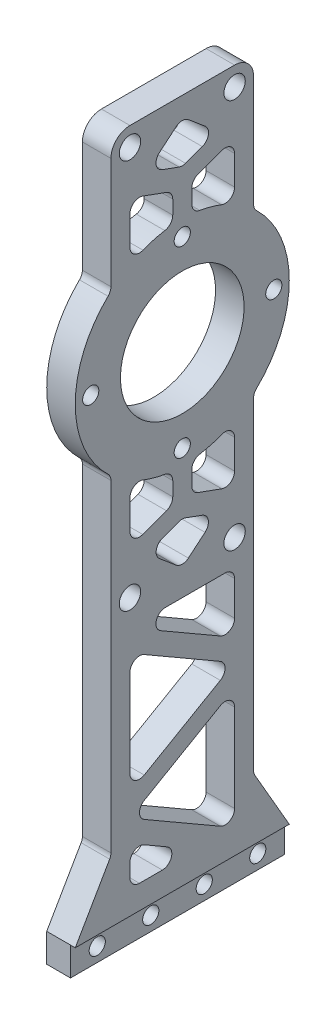
SolidWorks part; units mm, degrees
material "Сплав 2024"
ref_plane "Спереди" through (0, 0, 0) normal (0, 0, 1) x (1, 0, 0)
ref_plane "Сверху" through (0, 0, 0) normal (0, 1, 0) x (1, 0, 0)
ref_plane "Справа" through (0, 0, 0) normal (1, 0, 0) x (0, 0, -1)
sketch "Эскиз1" plane through (0, 0, 0) normal (0, 1, 0) x (1, 0, 0)
  line L1 (0, 0) -> (6, 0)
  line L2 (0, 0) -> (0, -30)
  line L3 (0, -30) -> (6, -30)
  line L4 (6, 0) -> (6, -30)
  dimension "D1" = 6
  dimension "D2" = 30
extrude "Бобышка-Вытянуть1" add sketch "Эскиз1" along normal blind 177
sketch "Эскиз2" plane through (0, 0, 0) normal (-1, 0, 0) x (0, 0, 1)
  line L0 (30, 105) -> (0, 105) construction
  line L3 (15, 177) -> (15, 0) construction
  line L4 (0, 177) -> (30, 177) construction
  line L5 (0, 0) -> (30, 0) construction
  line L6 (30, 0) -> (0, 0) construction
  circle A0 centre (15, 105) radius 22.5
  dimension "D1" = 45
  dimension "D2" = 105
extrude "Бобышка-Вытянуть2" add sketch "Эскиз2" against normal up to surface (6 mm away) up to face at (6, 88.5, 15)
sketch "Эскиз3" plane through (0, 0, 0) normal (-1, 0, 0) x (0, 0, 1)
  circle A0 centre (15, 105) radius 13
  dimension "D1" = 26
extrude "Вырез-Вытянуть1" cut sketch "Эскиз3" against normal through all
sketch "Эскиз4" plane through (6, 0, 0) normal (-1, 0, 0) x (0, 0, 1)
  line L0 (-7.5, 105) -> (37.5, 105) construction
  line L2 (15, 127.5) -> (15, 82.5) construction
  line L3 (30, 105) -> (0, 105) construction
  circle A0 centre (15, 105) radius 19.25 construction
  circle A1 centre (15, 105) radius 22.5 construction
  dimension "D1" = 38.5
  dimension "D2" = 90
hole_wizard "Отверстие с зазором M32" positions "Эскиз6" profile "Эскиз5" hole size "M3" standard "Ansi Metric" end condition up to next
sketch "Эскиз6" plane through (6, -25.0247, 7.2629) normal (-1, 0, 0) x (0, 0, 1)
  line L0 (-14.7629, 130.0247) -> (30.2371, 130.0247) construction
  line L1 (7.7371, 152.5247) -> (7.7371, 107.5247) construction
  circle A0 centre (7.7371, 130.0247) radius 19.25 construction
  point P0 (-11.5129, 130.0247)
  point P6 (7.7371, 110.7747)
  point P10 (26.9871, 130.0247)
  point P12 (7.7371, 149.2747)
sketch "Эскиз5" plane through (6, 105, -4.25) normal (0, 1, 0) x (0, 0, -1)
  line L0 (0, 0) -> (0, 6)
  line L1 (0, 6) -> (1.7, 6)
  line L2 (1.7, 6) -> (1.7, 0)
  line L5 (1.7, 0) -> (0, 0)
  line L11 (0, -6.35) -> (0, 107.95) construction
  dimension "Диаметр сквозного отверстия" = 3.4
  dimension "Глубина сквозного отверстия" = 6
sketch "Эскиз8" plane through (6, 0, 0) normal (1, 0, 0) x (0, 0, -1)
  line L0 (-15, 177) -> (-15, 0) construction
  line L1 (-30, 177) -> (0, 177) construction
  line L2 (-30, 0) -> (0, 0) construction
  line L3 (19.447, 105) -> (-49.447, 105) construction
  line L4 (0, 177) -> (0, 121.7705) construction
  line L5 (-26, 146) -> (-4, 146) construction
  line L6 (-26, 146) -> (-26, 64) construction
  line L7 (-26, 64) -> (-4, 64) construction
  line L8 (-4, 146) -> (-4, 64) construction
  line L9 (-26, 146) -> (-4, 64) construction
  line L11 (-30, 105) -> (0, 105) construction
  point P8 (-15, 105)
  point P9 (-15, 105)
  dimension "D1" = 4
  dimension "D2" = 82
  dimension "D4" = 22
hole_wizard "Отверстие с зазором M41" positions "Эскиз10" profile "Эскиз9" hole size "M4" standard "Ansi Metric" end condition through all
sketch "Эскиз10" plane through (6, 0, 0) normal (1, 0, 0) x (0, 0, -1)
  point P0 (-26, 146)
  point P3 (-4, 146)
  point P6 (-4, 64)
  point P9 (-26, 64)
sketch "Эскиз9" plane through (6, 146, 26) normal (0, 1, 0) x (0, 0, -1)
  line L0 (0, 0) -> (0, 6)
  line L1 (0, 6) -> (2.25, 6)
  line L2 (2.25, 6) -> (2.25, 0)
  line L5 (2.25, 0) -> (0, 0)
  line L11 (0, -6.35) -> (0, 107.95) construction
  dimension "Диаметр сквозного отверстия" = 4.5
  dimension "Глубина сквозного отверстия" = 6
sketch "Эскиз11" plane through (6, 0, 0) normal (1, 0, 0) x (0, 0, -1)
  line L0 (-30, 0) -> (0, 0) construction
  line L1 (-15, 177) -> (-15, 0) construction
  line L2 (-30, 177) -> (0, 177) construction
  line L3 (0, 88.2295) -> (0, 0) construction
  line L4 (-30, 88.2295) -> (-30, 0) construction
  line L5 (-37.5, 3) -> (7.5, 3) construction
  line L6 (-9.375, 6) -> (-9.375, 0) construction
  line L7 (-3.75, 6) -> (-3.75, 0) construction
  line L8 (1.875, 6) -> (1.875, 0) construction
  line L20 (-15, 0) -> (-15, 6) construction
  line L21 (-20.625, 0) -> (-20.625, 6) construction
  line L22 (-26.25, 0) -> (-26.25, 6) construction
  line L23 (-31.875, 0) -> (-31.875, 6) construction
  line L25 (-37.5, 0) -> (7.5, 6) construction
  line L26 (-37.5, 6) -> (7.5, 0) construction
  line L27 (-37.5, 6) -> (7.5, 6) construction
  line L28 (0, 18.9904) -> (7.5, 6)
  line L29 (-30, 18.9904) -> (0, 18.9904)
  line L30 (7.5, 6) -> (7.5, 0)
  line L31 (-37.5, 0) -> (7.5, 0)
  line L32 (-37.5, 6) -> (-37.5, 0)
  line L33 (-37.5, 6) -> (-30, 18.9904)
  point P2 (-15, 3)
  dimension "D1" = 45
  dimension "D2" = 6
  dimension "D3" = 5.625
  dimension "D4" = 5.625
  dimension "D5" = 5.625
  dimension "D6" = 5.625
  dimension "D7" = 120
  dimension "D8" = 5.625
  dimension "D9" = 5.625
  dimension "D10" = 5.625
extrude "Бобышка-Вытянуть3" add sketch "Эскиз11" against normal up to surface (6 mm away) up to face at (0, 146, 23.75)
hole_wizard "Отверстие с зазором M31" positions "Эскиз13" profile "Эскиз12" hole size "M3" standard "Ansi Metric" end condition through all
sketch "Эскиз13" plane through (6, 0, 0) normal (1, 0, 0) x (0, 0, -1)
  line L4 (-31.875, 0) -> (-31.875, 6) construction
  line L8 (1.875, 6) -> (1.875, 0) construction
  line L9 (-9.375, 6) -> (-9.375, 0) construction
  line L10 (-20.625, 0) -> (-20.625, 6) construction
  point P16 (-31.875, 3)
  point P20 (-20.625, 3)
  point P24 (-9.375, 3)
  point P28 (1.875, 3)
sketch "Эскиз12" plane through (6, 3, 31.875) normal (0, 1, 0) x (0, 0, -1)
  line L0 (0, 0) -> (0, 6)
  line L1 (0, 6) -> (1.7, 6)
  line L2 (1.7, 6) -> (1.7, 0)
  line L5 (1.7, 0) -> (0, 0)
  line L11 (0, -6.35) -> (0, 107.95) construction
  dimension "Диаметр сквозного отверстия" = 3.4
  dimension "Глубина сквозного отверстия" = 6
sketch "Эскиз14" plane through (6, 0, 0) normal (1, 0, 0) x (0, 0, -1)
  line L5 (-37.5, 0) -> (7.5, 0)
  line L6 (-37.5, 0) -> (-37.5, 6)
  line L7 (-37.5, 6) -> (7.5, 6)
  line L8 (7.5, 0) -> (7.5, 6)
extrude "Вырез-Вытянуть2" cut sketch "Эскиз14" against normal blind 1
sketch "Эскиз15" plane through (6, 0, 0) normal (1, 0, 0) x (0, 0, -1)
  line L0 (0, 177) -> (0, 121.7705) construction
  line L1 (-30, 177) -> (0, 177)
  line L2 (-30, 177) -> (-30, 150)
  line L3 (-30, 150) -> (0, 150)
  line L4 (0, 177) -> (0, 150)
  circle A0 centre (-26, 146) radius 2.25 construction
  dimension "D1" = 4
extrude "Вырез-Вытянуть3" cut sketch "Эскиз15" against normal up to surface (6 mm away) up to face at (0, 3, 30.175)
fillet "Скругление1" radius 4 2 edges at (3, 150, 30) (3, 150, 0)
sketch "Эскиз16" plane through (0, 0, 0) normal (-1, 0, 0) x (0, 0, 1)
  line L0 (4, 0) -> (4, 150) construction
  line L1 (-7.5, 0) -> (37.5, 0) construction
  line L2 (4, 150) -> (26, 150) construction
  line L3 (26, 0) -> (26, 150) construction
  line L4 (0, 88.2295) -> (0, 18.9904) construction
  line L5 (30, 88.2295) -> (30, 18.9904) construction
  line L6 (15, 177) -> (15, 0) construction
  line L7 (0, 146) -> (30, 146) construction
  line L8 (0, 146) -> (0, 121.7705) construction
  line L9 (30, 146) -> (30, 121.7705) construction
  line L10 (15, 146) -> (4, 136.7699) construction
  line L11 (15, 146) -> (26, 136.7699) construction
  line L12 (0, 136.7699) -> (30, 136.7699) construction
  line L13 (4, 136.7699) -> (4, 124.6278)
  line L14 (26, 136.7699) -> (26, 124.6278)
  line L15 (13, 133.4942) -> (13, 127.4109)
  line L16 (17, 133.4942) -> (17, 127.4109)
  line L17 (4, 136.7699) -> (13, 133.4942)
  line L18 (0, 133.4942) -> (30, 133.4942) construction
  line L19 (26, 136.7699) -> (17, 133.4942)
  line L20 (7.5382, 139.7388) -> (15, 137.0229)
  line L21 (22.4618, 139.7388) -> (15, 137.0229)
  line L22 (7.5382, 139.7388) -> (15, 146)
  line L23 (15, 146) -> (22.4618, 139.7388)
  line L24 (15, 105) -> (22.4618, 105) construction
  line L25 (13, 76.4791) -> (13, 82.5891)
  line L26 (17, 76.4791) -> (17, 82.5891)
  line L27 (26, 73.2033) -> (17, 76.4791)
  line L28 (26, 73.2033) -> (26, 85.3722)
  line L29 (4, 73.2033) -> (4, 85.3722)
  line L30 (4, 73.2033) -> (13, 76.4791)
  line L31 (7.5605, 70.2425) -> (15, 72.9503)
  line L32 (22.4395, 70.2425) -> (15, 72.9503)
  line L33 (15, 64) -> (22.4395, 70.2425)
  line L34 (7.5605, 70.2425) -> (15, 64)
  line L35 (26, 53.8812) -> (26, 28.4778)
  line L36 (26, 28.4778) -> (4, 41.1795)
  line L37 (4, 41.1795) -> (26, 53.8812)
  line L38 (4, 58.5) -> (26, 58.5)
  line L39 (26, 58.5) -> (4, 45.7983)
  line L40 (4, 45.7983) -> (4, 58.5)
  line L41 (4, 36.5607) -> (26, 23.859)
  line L42 (26, 23.859) -> (4, 11.1573)
  line L43 (4, 11.1573) -> (4, 36.5607)
  line L44 (11.7276, 11) -> (26, 19.2402)
  line L45 (26, 19.2402) -> (26, 11)
  line L46 (26, 11) -> (11.7276, 11)
  line L47 (34.6132, 11) -> (-4.6132, 11) construction
  line L48 (30, 18.9904) -> (37.5, 6) construction
  line L49 (-7.5, 6) -> (0, 18.9904) construction
  line L50 (-7.5, 6) -> (37.5, 6) construction
  line L51 (0, 76.4791) -> (30, 76.4791) construction
  line L52 (0, 73.2033) -> (30, 73.2033) construction
  line L53 (0, 70.2425) -> (30, 70.2425) construction
  line L54 (26, 64) -> (4, 64) construction
  circle A0 centre (15, 105) radius 22.5 construction
  arc A1 (4, 124.6278) -> (13, 127.4109) centre (15, 105) cw
  arc A2 (17, 127.4109) -> (26, 124.6278) centre (15, 105) cw
  arc A3 (17, 82.5891) -> (26, 85.3722) centre (15, 105) ccw
  arc A4 (4, 85.3722) -> (13, 82.5891) centre (15, 105) ccw
  circle A5 centre (4, 64) radius 2.25 construction
  point P12 (4, 124.6278)
  point P13 (26, 124.6278)
  point P20 (15, 146)
  dimension "D3" = 4
  dimension "D16" = 5.5
  dimension "D1" = 4
  dimension "D2" = 4
  dimension "D4" = 100
  dimension "D5" = 4
  dimension "D6" = 2
  dimension "D7" = 4
  dimension "D8" = 110
  dimension "D9" = 30
  dimension "D10" = 4
  dimension "D11" = 4
  dimension "D12" = 4
  dimension "D13" = 60
  dimension "D14" = 60
  dimension "D15" = 5
  dimension "D17" = 6.11
  dimension "D18" = 4
  dimension "D19" = 2
  dimension "D20" = 110
  dimension "D21" = 4
  dimension "D22" = 100
extrude "Вырез-Вытянуть4" cut sketch "Эскиз16" against normal through all
fillet "Скругление3" radius 2 42 edges at (3, 127.4109, 13) (3, 124.6278, 26) (3, 124.6278, 4) (3, 127.4109, 17) (3, 133.4942, 17) (3, 136.7699, 4) (3, 133.4942, 13) (3, 136.7699, 26) (3, 137.0229, 15) (3, 139.7388, 22.4618) (3, 139.7388, 7.5382) (3, 146, 15) (3, 70.2425, 7.5605) (3, 70.2425, 22.4395) (3, 85.3722, 4) (3, 76.4791, 17) (3, 82.5891, 17) (3, 73.2033, 4) (3, 64, 15) (3, 72.9503, 15) (3, 82.5891, 13) (3, 85.3722, 26) (3, 76.4791, 13) (3, 73.2033, 26) (3, 11, 11.7276) (3, 11, 26) (3, 11.1573, 4) (3, 19.2402, 26) (3, 23.859, 26) (3, 28.4778, 26) (3, 36.5607, 4) (3, 53.8812, 26) (3, 41.1795, 4) (3, 45.7983, 4) (3, 58.5, 4) (3, 58.5, 26) (3, 18.9904, 30) (3, 18.9904, 0) (3, 121.7705, 0) (3, 121.7705, 30) (3, 88.2295, 30) (3, 88.2295, 0)
equation "\"D4@Эскиз11\"=\"D3@Эскиз11\""
equation "\"D5@Эскиз11\"=\"D3@Эскиз11\""
equation "\"D6@Эскиз11\"=\"D4@Эскиз11\""
equation "\"D3@Эскиз11\"=\"D1@Эскиз11\" / 8"
equation "\"D13@Эскиз16\"=\"D9@Эскиз16\"*2"
equation "\"D11@Эскиз16\"=\"D10@Эскиз16\""
equation "\"D12@Эскиз16\"=\"D10@Эскиз16\""
equation "\"D8@Эскиз11\"=\"D3@Эскиз11\""
equation "\"D9@Эскиз11\"=\"D3@Эскиз11\""
equation "\"D10@Эскиз11\"=\"D3@Эскиз11\""
